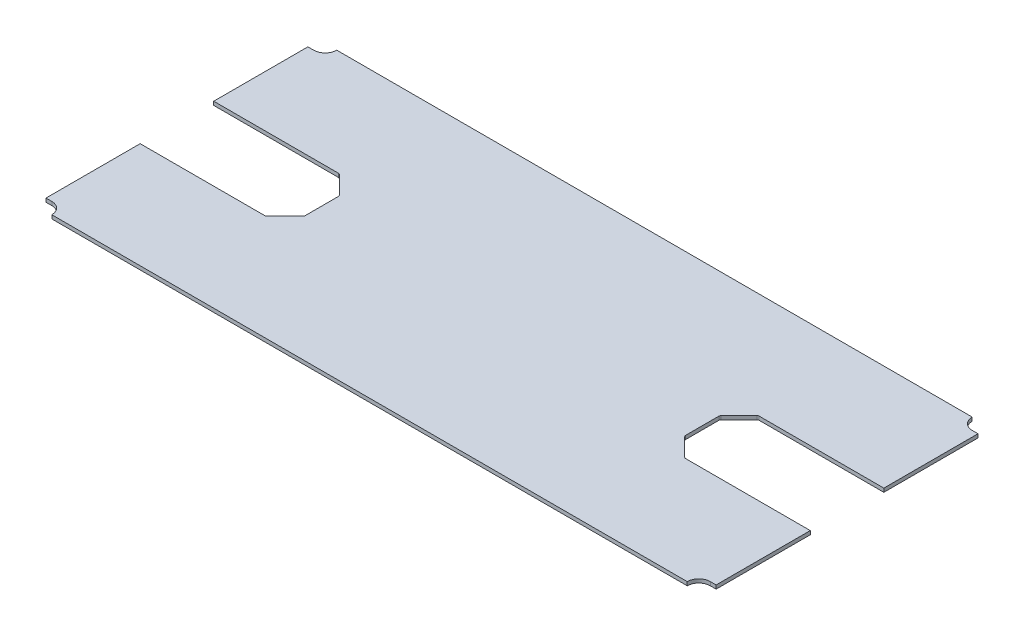
SolidWorks part; units mm, degrees
material "Mahogany"
ref_plane "Front Plane" through (0, 0, 0) normal (0, 0, 1) x (1, 0, 0)
ref_plane "Top Plane" through (0, 0, 0) normal (0, 1, 0) x (1, 0, 0)
ref_plane "Right Plane" through (0, 0, 0) normal (1, 0, 0) x (0, 0, -1)
sketch "Sketch1" plane through (0, 0, 0) normal (0, 1, 0) x (1, 0, 0)
  line L0 (-870, 95.5) -> (-494, 95.5)
  line L1 (-870, 370) -> (870, 370)
  line L2 (-870, 370) -> (-870, -370)
  line L3 (-870, -370) -> (870, -370)
  line L4 (870, 370) -> (870, -370)
  line L5 (-870, 370) -> (870, -370) construction
  line L6 (-870, -370) -> (870, 370) construction
  line L23 (-494, 95.5) -> (-494, -95.5)
  line L24 (-494, -95.5) -> (-870, -95.5)
  line L25 (870, 95.5) -> (494, 95.5)
  line L26 (494, 95.5) -> (494, -95.5)
  line L27 (494, -95.5) -> (870, -95.5)
  line L28 (-870, 340) -> (-855, 340)
  line L29 (0, -370) -> (0, 370) construction
  line L30 (-870, 0) -> (870, 0) construction
  line L31 (-870, -340) -> (-855, -340)
  line L32 (870, 340) -> (855, 340)
  line L33 (870, -340) -> (855, -340)
  arc A0 (-855, 340) -> (-825, 370) centre (-855, 370) ccw
  arc A1 (-855, -340) -> (-825, -370) centre (-855, -370) cw
  arc A2 (855, 340) -> (825, 370) centre (855, 370) cw
  arc A3 (855, -340) -> (825, -370) centre (855, -370) ccw
  point P0 (0, 0)
  point P26 (494, 0)
  point P27 (-494, 0)
  dimension "D6" = 30
  dimension "D4" = 376
  dimension "D5" = 191
  dimension "D2" = 740
  dimension "D1" = 1740
  dimension "D3" = 15
extrude "Boss-Extrude1" add sketch "Sketch1" along normal blind 9.525 contours L27 L26 L25 L4 L1 L2 L0 L23 L24 L3 region at (0, 0, 0)
chamfer "Chamfer1" distance 50 angle 45 4 edges at (494, 4.7625, 95.5) (494, 4.7625, -95.5) (-494, 4.7625, 95.5) (-494, 4.7625, -95.5)
fillet "Fillet2" radius 5 8 edges at (494, 4.7625, -45.5) (494, 4.7625, 45.5) (544, 4.7625, 95.5) (544, 4.7625, -95.5) (-544, 4.7625, 95.5) (-494, 4.7625, 45.5) (-494, 4.7625, -45.5) (-544, 4.7625, -95.5)
equation "\"W\"= 1750"
equation "\"L\"= 780"
equation "\"H\"= 780"
equation "\"ARM_BOLT_SPACING\"= 166"
equation "\"ARM_TO_WALL\"= 200"
equation "\"D4@Sketch1\"=\"ARM_TO_WALL\"+\"ARM_BOLT_SPACING\"+10"
equation "\"D5@Sketch1\"=\"ARM_BOLT_SPACING\"+25"
equation "\"D2@Sketch1\"=\"L\"-40"
equation "\"D1@Sketch1\"=\"W\"-10"
